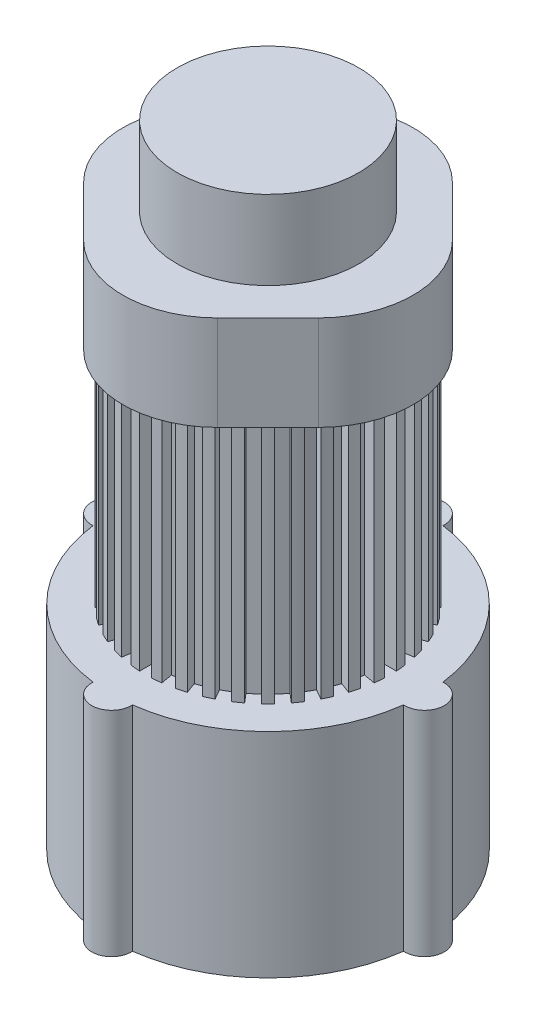
SolidWorks part; units mm, degrees
ref_plane "前视基准面" through (0, 0, 0) normal (0, 0, 1) x (1, 0, 0)
ref_plane "上视基准面" through (0, 0, 0) normal (0, 1, 0) x (1, 0, 0)
ref_plane "右视基准面" through (0, 0, 0) normal (1, 0, 0) x (0, 0, -1)
sketch "草图1" plane through (0, 0, 0) normal (0, 1, 0) x (1, 0, 0)
  circle A0 centre (0, 0) radius 8.2
  dimension "D1" = 16.4
extrude "凸台-拉伸1" add sketch "草图1" along normal blind 1
sketch "草图2" plane through (0, 1, 0) normal (0, 1, 0) x (1, 0, 0)
  line L0 (0, 12.8701) -> (0, -12.5799) construction
  line L1 (0, 0) -> (17.876, 0) construction
  circle A0 centre (0, 0) radius 19.799
  circle A2 centre (0, 19.799) radius 2.5
  circle A3 centre (19.799, 0) radius 2.5
  circle A4 centre (0, -19.799) radius 2.5
  circle A5 centre (-19.799, 0) radius 2.5
  point P3 (0, 0)
  point P4 (0, 0)
  point P9 (0, 10.2)
  point P19 (0, 0)
  circle M4 centre (0, 0) radius 8.2
  dimension "D2" = 5
  dimension "D3" = 4
  dimension "D4" = 28
extrude "凸台-拉伸2" add sketch "草图2" along normal blind 27 contours A5 A0 A4 A3 A2 M4 | M4 | A0 A3 | A0 A3 | A0 A2 | A0 A2 | A0 A5 | A0 A5 | A0 A4 | A0 A4 | A0 region at (18.71, 1, 0) region at (20.8311, 1, 0) region at (16.7435, 1, 0) region at (0, 1, -18.71) region at (0, 1, -20.8311) region at (0, 1, 20.8311) region at (0, 1, 18.71) region at (-18.71, 1, 0) region at (-20.8311, 1, 0) region at (0, 1, 0)
sketch "草图3" plane through (0, 28, 0) normal (0, 1, 0) x (1, 0, 0)
  circle A0 centre (0, 0) radius 15.5
  dimension "D1" = 31
extrude "凸台-拉伸4" add sketch "草图3" along normal offset from surface (43 mm away) 70 up to face at (0, 1, 8.2)
sketch "草图4" plane through (0, 71, 0) normal (0, 1, 0) x (1, 0, 0)
  circle A0 centre (0, 0) radius 11.5
  dimension "D1" = 23
extrude "凸台-拉伸5" add sketch "草图4" along normal blind 10
sketch "草图5" plane through (0, 71, 0) normal (0, 1, 0) x (1, 0, 0)
  line L0 (-19.799, 0) -> (0, 19.799) construction
  line L1 (-14.8492, 8.4853) -> (-8.4853, 14.8492)
  line L2 (8.4853, 14.8492) -> (14.8492, 8.4853)
  line L3 (14.8492, -8.4853) -> (8.4853, -14.8492)
  line L4 (-8.4853, -14.8492) -> (-14.8492, -8.4853)
  line L5 (-23.3345, 0) -> (23.3345, 0) construction
  line L6 (0, 23.3345) -> (0, -23.3345) construction
  arc A0 (-14.8492, -8.4853) -> (-14.8492, 8.4853) centre (-6.364, 0) cw
  arc A1 (2.495, 19.6412) -> (-2.495, 19.6412) centre (0, 19.799) ccw construction
  arc A2 (-19.6412, 2.495) -> (-19.6412, -2.495) centre (-19.799, 0) ccw construction
  arc A3 (2.495, 19.6412) -> (-2.495, 19.6412) centre (0, 19.799) ccw construction
  arc A4 (-19.6412, 2.495) -> (-19.6412, -2.495) centre (-19.799, 0) ccw construction
  arc A5 (8.4853, -14.8492) -> (-8.4853, -14.8492) centre (0, -6.364) cw
  arc A6 (14.8492, 8.4853) -> (14.8492, -8.4853) centre (6.364, 0) cw
  arc A7 (-8.4853, 14.8492) -> (8.4853, 14.8492) centre (0, 6.364) cw
  point P6 (0, 0)
  point P8 (1.0583, 0.9405)
  point P12 (0, 0)
  dimension "D2" = 33
  dimension "D1" = 12
extrude "凸台-拉伸6" add sketch "草图5" against normal blind 12
sketch "草图6" plane through (0, 28, 0) normal (0, 1, 0) x (1, 0, 0)
  line L0 (0, 0) -> (-18.4515, 0) construction
  line L2 (-17, -0.75) -> (-14, -0.75)
  line L3 (-17, -0.75) -> (-17, 0.75)
  line L4 (-17, 0.75) -> (-14, 0.75)
  line L5 (-14, -0.75) -> (-14, 0.75)
  line L6 (-17, -0.75) -> (-14, 0.75) construction
  line L7 (-17, 0.75) -> (-14, -0.75) construction
  circle A0 centre (0, 0) radius 15.5 construction
  circle A1 centre (0, 0) radius 15.5
  point P3 (-15.5, 0)
  circle M4 centre (0, 0) radius 15.5
  dimension "D1" = 1.5
  dimension "D2" = 3
extrude "切除-拉伸1" cut sketch "草图6" along normal up to surface (31 mm away) contours L4 L3 L2 M4 | L2 L5 L4 M4 region at (-16.247, 28, 0) region at (-14.747, 28, 0) up to face at (0, 59, -15.5)
pattern_circular "阵列(圆周)1" count 36 every 10 about axis through (0, 184.8406, 0) along (0, -1, 0) of "切除-拉伸1" reverse direction yes
sketch "草图7" plane through (0, 0, 0) normal (0, -1, 0) x (1, 0, 0)
  circle A1 centre (0, 0) radius 2.5
  dimension "D1" = 5
extrude "凸台-拉伸7" add sketch "草图7" along normal blind 10
ref_plane "基准面1" through (0, -9, 0) normal (0, -1, 0) x (-1, 0, 0)
sketch "草图9" plane through (0, -9, 0) normal (0, -1, 0) x (-1, 0, 0)
  line L1 (2.5, 0) -> (0, -2.5)
  line L2 (0, -2.5) -> (-2.5, 0)
  circle A1 centre (0, 0) radius 2.5
  arc A2 (-2.5, 0) -> (2.5, 0) centre (0, 0) ccw
  dimension "D1" = 0
extrude "切除-拉伸2" cut sketch "草图9" against normal blind 5 contours L2 A2 | L1 A2 region at (-1.4599, -9, 1.4599) region at (1.4599, -9, 1.4599)
sketch "草图10" plane through (0, 1, 0) normal (0, -1, 0) x (1, 0, 0)
  line L0 (-19.799, 0) -> (0, -19.799) construction
  line L1 (0, 0) -> (-9.8995, -9.8995) construction
  circle A0 centre (0, 0) radius 14.3677 construction
  arc A1 (-2.495, -19.6412) -> (2.495, -19.6412) centre (0, -19.799) ccw construction
  arc A2 (-19.6412, 2.495) -> (-19.6412, -2.495) centre (-19.799, 0) ccw construction
  arc A3 (-2.495, -19.6412) -> (2.495, -19.6412) centre (0, -19.799) ccw construction
  arc A4 (-19.6412, 2.495) -> (-19.6412, -2.495) centre (-19.799, 0) ccw construction
  circle A5 centre (-10.1595, -10.1595) radius 1.5
  circle A6 centre (-3.7186, 13.8781) radius 1.5
  circle A7 centre (13.8781, -3.7186) radius 1.5
  point P19 (0, 0)
  dimension "D1" = 3
  dimension "D2" = 3
extrude "切除-拉伸3" cut sketch "草图10" against normal blind 15
